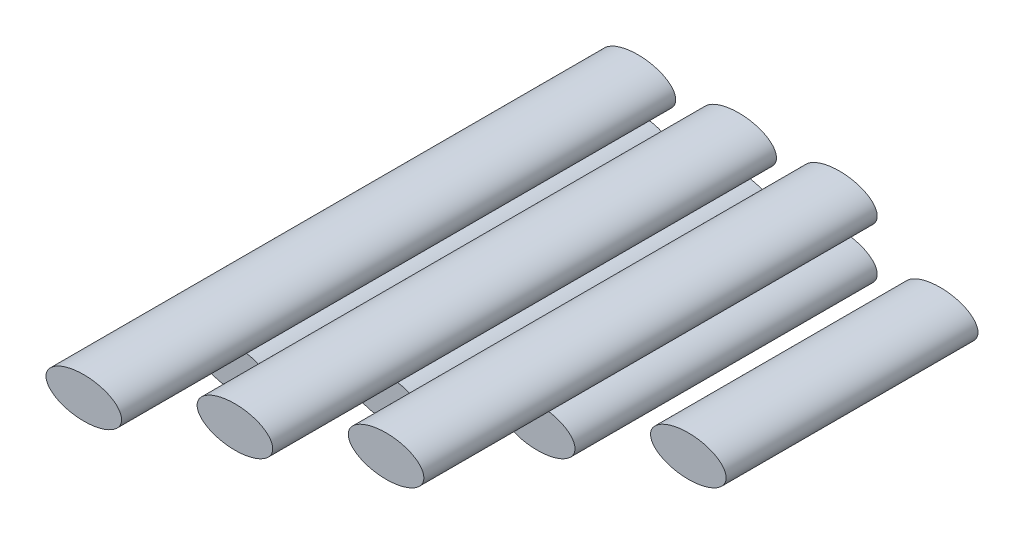
SolidWorks part; units mm, degrees
ref_plane "Front Plane" through (0, 0, 0) normal (0, 0, 1) x (1, 0, 0)
ref_plane "Top Plane" through (0, 0, 0) normal (0, 1, 0) x (1, 0, 0)
ref_plane "Right Plane" through (0, 0, 0) normal (1, 0, 0) x (0, 0, -1)
sketch "Sketch2" plane through (0, 0, 0) normal (0, 0, 1) x (1, 0, 0)
  ellipse E0 centre (0, 0) end of major axis (-1.5, 0) minor radius 0.8
  ellipse E1 centre (4, 0) end of major axis (2.5, 0) minor radius 0.8
  ellipse E2 centre (8, 0) end of major axis (6.5, 0) minor radius 0.8
  ellipse E3 centre (12, 0) end of major axis (10.5, 0) minor radius 0.8
  ellipse E4 centre (4, 2) end of major axis (2.5, 2) minor radius 0.8
  ellipse E5 centre (8, 2) end of major axis (6.5, 2) minor radius 0.8
  ellipse E7 centre (0, 2) end of major axis (-1.5, 2) minor radius 0.8
extrude "Boss-Extrude1" add sketch "Sketch2" along normal blind 10 contours E3
extrude "Boss-Extrude2" add sketch "Sketch2<3>" along normal blind 12 separate body contours E2
sketch "Sketch2<3>" plane through (0, 0, 0) normal (0, 0, 1) x (1, 0, 0) same geometry as "Sketch2"
extrude "Boss-Extrude3" add sketch "Sketch2<4>" along normal blind 14 separate body contours E1
sketch "Sketch2<4>" plane through (0, 0, 0) normal (0, 0, 1) x (1, 0, 0) same geometry as "Sketch2"
extrude "Boss-Extrude4" add sketch "Sketch2<5>" along normal blind 16 separate body contours E0
sketch "Sketch2<5>" plane through (0, 0, 0) normal (0, 0, 1) x (1, 0, 0) same geometry as "Sketch2"
extrude "Boss-Extrude5" add sketch "Sketch2<6>" along normal blind 18 separate body contours E5
sketch "Sketch2<6>" plane through (0, 0, 0) normal (0, 0, 1) x (1, 0, 0) same geometry as "Sketch2"
extrude "Boss-Extrude6" add sketch "Sketch2<7>" along normal blind 20 separate body contours E4
sketch "Sketch2<7>" plane through (0, 0, 0) normal (0, 0, 1) x (1, 0, 0) same geometry as "Sketch2"
extrude "Boss-Extrude7" add sketch "Sketch2<8>" along normal blind 22 separate body contours E7
sketch "Sketch2<8>" plane through (0, 0, 0) normal (0, 0, 1) x (1, 0, 0) same geometry as "Sketch2"
